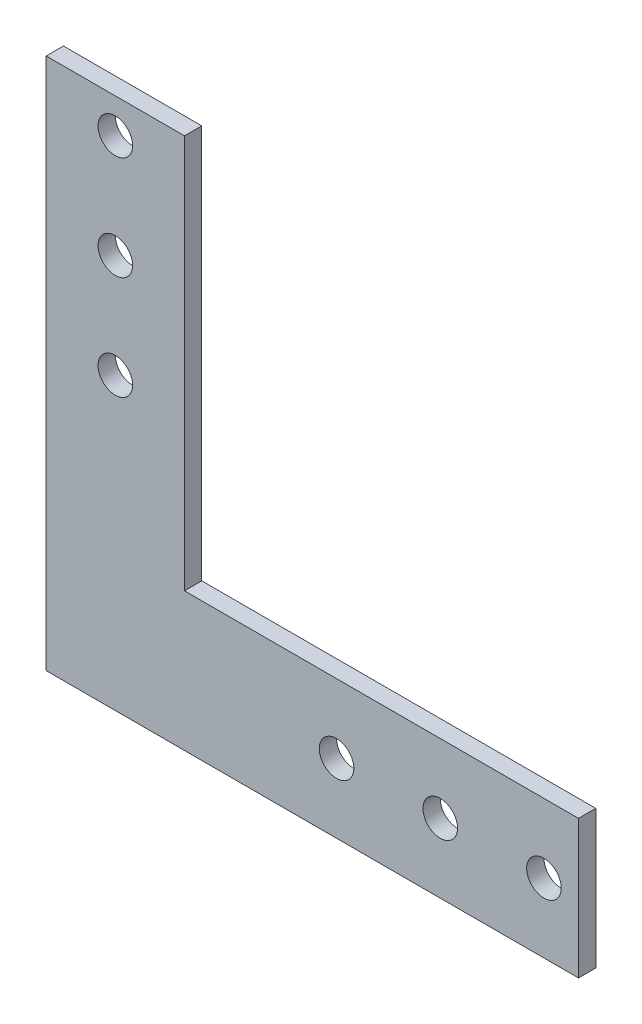
SolidWorks part; units mm, degrees
ref_plane "Front Plane" through (0, 0, 0) normal (0, 0, 1) x (1, 0, 0)
ref_plane "Top Plane" through (0, 0, 0) normal (0, 1, 0) x (1, 0, 0)
ref_plane "Right Plane" through (0, 0, 0) normal (1, 0, 0) x (0, 0, -1)
sketch "Sketch1" plane through (0, 0, 0) normal (0, 0, 1) x (1, 0, 0)
  line L1 (0, 0) -> (25.4, 0)
  line L2 (0, 0) -> (0, 97.79)
  line L3 (0, 97.79) -> (25.4, 97.79)
  line L4 (25.4, 25.4) -> (25.4, 79.8295)
  line L5 (0, 0) -> (97.79, 0)
  line L6 (0, 0) -> (0, 25.4)
  line L7 (25.4, 25.4) -> (79.8295, 25.4)
  line L8 (97.79, 0) -> (97.79, 25.4)
  line L11 (25.4, 97.79) -> (25.4, 79.8295)
  line L12 (79.8295, 25.4) -> (97.79, 25.4)
  dimension "D1" = 25.4
  dimension "D2" = 25.4
  dimension "D3" = 97.79
  dimension "D4" = 97.79
  dimension "D7" = 17.9605
extrude "Boss-Extrude1" add sketch "Sketch1" along normal blind 3.175 contours L5 L8 L7 L4 L3 L2 L1 region at (1.383, 12.7, 0)
sketch "Sketch2" plane through (0, 0, 3.175) normal (0, 0, 1) x (1, 0, 0)
  line L0 (0, 0) -> (97.79, 0) construction
  line L1 (0, 0) -> (0, 97.79) construction
  line L2 (25.4, 25.4) -> (97.79, 25.4) construction
  circle A0 centre (53.34, 12.7) radius 3.175
  circle A1 centre (72.39, 12.7) radius 3.175
  circle A2 centre (12.7, 53.34) radius 3.175
  circle A3 centre (12.7, 72.39) radius 3.175
  circle A4 centre (12.7, 91.44) radius 3.175
  circle A5 centre (91.44, 12.7) radius 3.175
  dimension "D5" = 6.35
  dimension "D6" = 6.35
  dimension "D7" = 6.35
  dimension "D8" = 6.35
  dimension "D9" = 6.35
  dimension "D10" = 6.35
  dimension "D1" = 53.34
  dimension "D2" = 53.34
  dimension "D3" = 19.05
  dimension "D4" = 19.05
  dimension "D11" = 19.05
  dimension "D12" = 19.05
  dimension "D13" = 12.7
  dimension "D14" = 12.7
  dimension "D15" = 12.7
  dimension "D16" = 12.7
  dimension "D17" = 12.7
  dimension "D18" = 12.7
extrude "Cut-Extrude1" cut sketch "Sketch2" against normal through all
sketch "Sketch3" plane through (0, 0, 3.175) normal (0, 0, 1) x (1, 0, 0)
